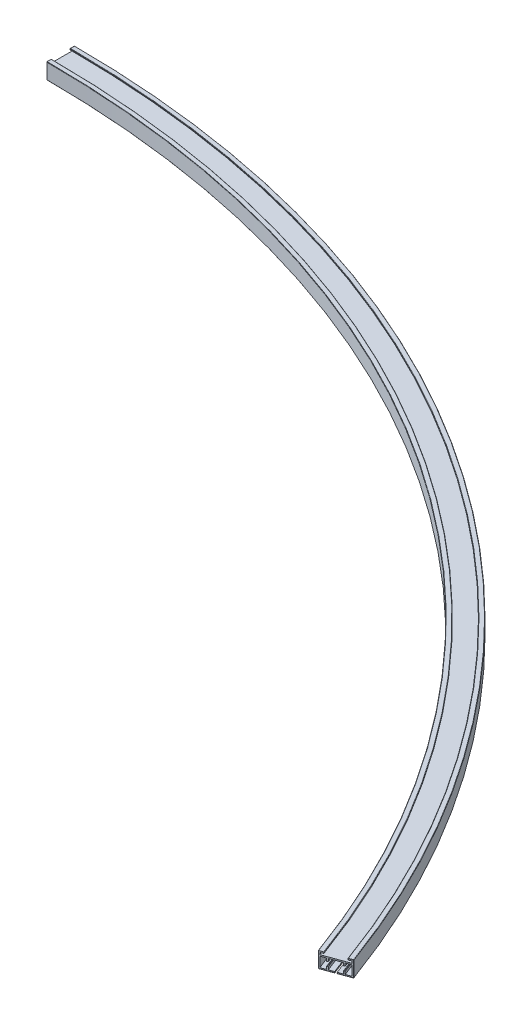
SolidWorks part; units mm, degrees
ref_plane "前视基准面" through (0, 0, 0) normal (0, 0, 1) x (1, 0, 0)
ref_plane "上视基准面" through (0, 0, 0) normal (0, 1, 0) x (1, 0, 0)
ref_plane "右视基准面" through (0, 0, 0) normal (1, 0, 0) x (0, 0, -1)
sketch "草图1" plane through (0, 0, 0) normal (1, 0, 0) x (0, 0, -1)
  line L0 (0, 0) -> (0, -17) construction
  line L1 (-15, 5) -> (-20, 5) construction
  line L2 (-20, 5) -> (-20, -17) construction
  line L3 (-20, -17) -> (-3, -17) construction
  line L4 (-20, 0) -> (20, 0) construction
  line L5 (-10, 0) -> (-10, -5.5) construction
  line L6 (10, 0) -> (10, -5.5) construction
  line L7 (20, -17) -> (3, -17) construction
  line L8 (20, 5) -> (20, -17) construction
  line L9 (15, 5) -> (20, 5) construction
  line L10 (-1480, 82.1192) -> (-1480, -100.4998) construction
  line L11 (-21, 6) -> (-14, 6)
  line L12 (-14, 6) -> (-14, 4)
  line L13 (-14, 4) -> (-19, 4)
  line L14 (-19, 4) -> (-19, 1)
  line L15 (-19, 1) -> (-0.0467, 1)
  line L16 (-21, 6) -> (-21, -18)
  line L17 (-21, -18) -> (-1.5207, -18)
  line L18 (-1.5207, -18) -> (-1.5207, -16)
  line L19 (-1.5207, -16) -> (-9, -16)
  line L20 (-9, -16) -> (-9, -11.5)
  line L21 (-9, -1) -> (9, -1)
  line L22 (-19, -1) -> (-11, -1)
  line L23 (-11, -1) -> (-11, -5.5)
  line L24 (-11, -16) -> (-19, -16)
  line L25 (-19, -16) -> (-19, -1)
  line L26 (1.5207, -18) -> (1.5207, -16)
  line L27 (1.5207, -16) -> (9, -16)
  line L28 (9, -16) -> (9, -11.5)
  line L29 (21, -18) -> (1.5207, -18)
  line L30 (11, -16) -> (19, -16)
  line L31 (11, -1) -> (11, -5.5)
  line L32 (19, -16) -> (19, -1)
  line L33 (19, -1) -> (11, -1)
  line L34 (19, 1) -> (0.0467, 1)
  line L35 (19, 4) -> (19, 1)
  line L36 (21, 6) -> (21, -18)
  line L37 (14, 4) -> (19, 4)
  line L38 (14, 6) -> (14, 4)
  line L39 (21, 6) -> (14, 6)
  line L40 (-0.0467, 1) -> (0.0467, 1)
  line L41 (-11, -5.5) -> (-9, -5.5)
  line L42 (-11, -11.5) -> (-9, -11.5)
  line L43 (-11, -11.5) -> (-11, -16)
  line L44 (-10, -11.5) -> (-10, -17) construction
  line L45 (-9, -5.5) -> (-9, -1)
  line L47 (9, -5.5) -> (9, -1)
  line L48 (10, -11.5) -> (10, -17) construction
  line L49 (11, -11.5) -> (11, -16)
  line L50 (9, -5.5) -> (11, -5.5)
  line L51 (9, -11.5) -> (11, -11.5)
  point P44 (0, -1)
  dimension "D1" = 40
  dimension "D2" = 5
  dimension "D3" = 5
  dimension "D4" = 17
  dimension "D5" = 10
  dimension "D6" = 7
  dimension "D7" = 1500
  dimension "D8" = 1
  dimension "D9" = 1
  dimension "D10" = 1
  dimension "D11" = 1
  dimension "D12" = 1
  dimension "D13" = 1
  dimension "D14" = 1
  dimension "D15" = 1
  dimension "D16" = 19.4793
  dimension "D17" = 1
  dimension "D18" = 1
  dimension "D19" = 1
  dimension "D20" = 1
  dimension "D21" = 1
revolve "旋转1" add sketch "草图1" angle 70 about L10
fillet "圆角1" radius 0.5 15 edges at (0, 6, -17.5) (860.9382, 6, 250.4528) (1407.1897, 6, 967.8248) (856.9232, 6, 256.1868) (0, -6, 21) (836.848, 6, 284.8572) (1371.0115, -6, 980.9926) (836.848, -18, 284.8572) (856.9232, 4, 256.1868) (860.9382, -18, 250.4528) (1410.4786, -6, 966.6278) (1401.3263, -18, 969.9589) (1380.1638, -18, 977.6615) (840.8631, 4, 279.1231) (840.8631, 6, 279.1231)
fillet "圆角2" radius 0.5 16 edges at (0, -5.5, 10) (842.5838, -5.5, 276.6656) (1381.3482, -5.5, 977.2304) (843.7309, -5.5, 275.0273) (0, -11.5, -10) (855.2025, -11.5, 258.6443) (1400.142, -11.5, 970.39) (854.0553, -11.5, 260.2826) (0, -5.5, -10) (854.0553, -5.5, 260.2826) (1400.142, -5.5, 970.39) (855.2025, -5.5, 258.6443) (0, -11.5, 10) (843.7309, -11.5, 275.0273) (1381.3482, -11.5, 977.2304) (842.5838, -11.5, 276.6656)
ref_plane "基准面1" through (695.3725, 0, 486.9051) normal (-0.8192, 0, -0.5736) x (-0.5736, 0, 0.8192)
sketch "草图2" plane through (0, 0, 0) normal (0, 1, 0) x (1, 0, 0)
  circle A0 centre (0, -1480) radius 1500.5 construction
sketch "草图3" plane through (0, -18, 0) normal (0, -1, 0) x (1, 0, 0)
  circle A0 centre (0, 1480) radius 1480 construction
  dimension "D1" = 2960
